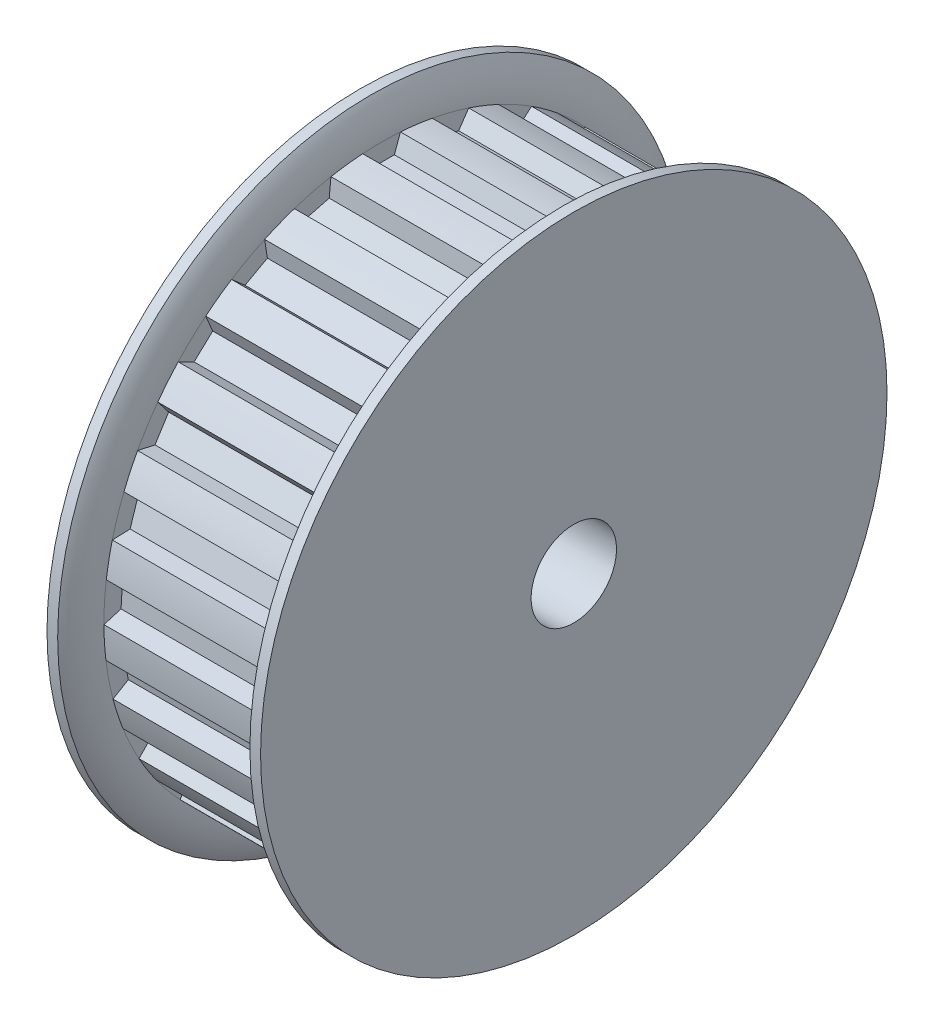
SolidWorks part; units mm, degrees
ref_plane "Front Plane" through (0, 0, 0) normal (0, 0, 1) x (1, 0, 0)
ref_plane "Top Plane" through (0, 0, 0) normal (0, 1, 0) x (1, 0, 0)
ref_plane "Right Plane" through (0, 0, 0) normal (1, 0, 0) x (0, 0, -1)
sketch "Sketch1" plane through (0, 0, 0) normal (1, 0, 0) x (0, 0, -1)
  line L3 (0, 0) -> (0, 18.3) construction
  line L6 (0, 18.3) -> (0, 19.5) construction
  line L7 (-1.325, 19.4549) -> (-0.8966, 18.278)
  line L8 (1.325, 19.4549) -> (0.8966, 18.278)
  line L9 (0, -2.2) -> (0, -3.2) construction
  line L10 (0, 20) -> (0, 19.5) construction
  line L12 (-0.8966, 18.278) -> (0.8966, 18.278)
  line L15 (0, 0) -> (0, -2.2) construction
  circle A0 centre (0, 0) radius 20 construction
  circle A1 centre (0, 0) radius 18.3 construction
  arc A7 (1.325, 19.4549) -> (-1.325, 19.4549) centre (0, 0) ccw
  dimension "PD" = 40
  dimension "D1" = 40
  dimension "D3" = 0.5
  dimension "D2" = 1.2
  dimension "D4" = 2.65
sketch "Sketch2" plane through (0, 0, 0) normal (0, 0, 1) x (1, 0, 0)
  line L0 (-10.5, 0) -> (10.5, 0) construction
  line L1 (-10.5, 3) -> (10.5, 3)
  line L2 (-10.5, 3) -> (-10.5, 13)
  line L3 (-4.5, 22) -> (-3.75, 22)
  line L4 (-3, 19.5) -> (-4.5, 19.5) construction
  line L5 (9.75, 19.5) -> (9.75, 22) construction
  line L6 (-3, 19.5) -> (9, 19.5)
  line L8 (9, 19.5) -> (10.5, 19.5) construction
  line L9 (9.75, 22) -> (10.5, 22)
  line L10 (10.5, 22) -> (10.5, 3)
  line L12 (-7.5, 13) -> (-7.5, 3) construction
  line L13 (-4.5, 22) -> (-4.5, 13)
  line L14 (-4.5, 13) -> (-10.5, 13)
  arc A0 (9, 19.5) -> (9.75, 22) centre (13.5417, 19.5) cw
  arc A1 (-3, 19.5) -> (-3.75, 22) centre (-7.5417, 19.5) ccw
  point P19 (-3, 19.5)
  point P20 (9, 19.5)
  dimension "Bore Size" = 6
  dimension "Overall Width" = 21
  dimension "Inside Width" = 12
  dimension "Outside Width" = 15
  dimension "Hub Dia" = 26
  dimension "OD" = 44
sketch "Sketch6" plane through (0, 0, 0) normal (0, 0, 1) x (1, 0, 0)
  line L0 (9.75, 22) -> (10.5, 22) construction
  line L1 (-3, 19.5) -> (9, 19.5) construction
  line L2 (-4.5, 22) -> (-3.75, 22) construction
  line L3 (-4.5, 22) -> (-4.5, 13) construction
  line L4 (-4.5, 13) -> (-10.5, 13) construction
  line L5 (-10.5, 3) -> (-10.5, 13) construction
  line L6 (-10.5, 3) -> (10.5, 3) construction
  line L7 (10.5, 22) -> (10.5, 3) construction
  line L8 (9.75, 22) -> (10.5, 22)
  line L9 (-3, 19.5) -> (9, 19.5)
  line L10 (-4.5, 22) -> (-3.75, 22)
  line L11 (-4.5, 22) -> (-4.5, 13)
  line L12 (-4.5, 13) -> (-10.5, 13)
  line L13 (-10.5, 3) -> (-10.5, 13)
  line L14 (-10.5, 3) -> (10.5, 3)
  line L15 (10.5, 22) -> (10.5, 3)
  arc A0 (9.75, 22) -> (9, 19.5) centre (13.5417, 19.5) ccw construction
  arc A1 (-3, 19.5) -> (-3.75, 22) centre (-7.5417, 19.5) ccw construction
  arc A2 (9.75, 22) -> (9, 19.5) centre (13.5417, 19.5) ccw
  arc A3 (-3, 19.5) -> (-3.75, 22) centre (-7.5417, 19.5) ccw
revolve "Revolve1" add sketch "Sketch6" angle 360 about L0
sketch "Sketch3" plane through (0, 0, 0) normal (1, 0, 0) x (0, 0, -1)
  line L2 (-1.325, 19.4549) -> (-0.8966, 18.278) construction
  line L3 (-0.8966, 18.278) -> (0.8966, 18.278) construction
  line L4 (1.325, 19.4549) -> (0.8966, 18.278) construction
  line L5 (-1.325, 19.4549) -> (-0.8966, 18.278)
  line L6 (-0.8966, 18.278) -> (0.8966, 18.278)
  line L7 (1.325, 19.4549) -> (0.8966, 18.278)
  arc A1 (1.325, 19.4549) -> (-1.325, 19.4549) centre (0, 0) ccw construction
  arc A2 (1.325, 19.4549) -> (-1.325, 19.4549) centre (0, 0) ccw
extrude "Cut-Extrude1" cut sketch "Sketch3" along normal up to vertex (9 mm away) from vertex up to point (9, 19.5, 0) starting at point (-3, 19.5, 0)
pattern_circular "CirPattern1" count 25 over 360 about axis through (-10.5, 0, 0) along (-1, 0, 0) of "Cut-Extrude1"
sketch "Sketch5" plane through (0, 0, 0) normal (0, 0, 1) x (1, 0, 0)
  line L0 (-10.5, 0) -> (10.5, 0) construction
  point P0 (9, 0)
ref_axis "Center Axis 1" through (10.5, 0, 0) along (-1, 0, 0)
equation "\"D3@Sketch1\" = \"ht@Sketch1\" / 2"
equation "\"D2@Sketch1\" = \"hs@Sketch1\" - \"ht@Sketch1\""
